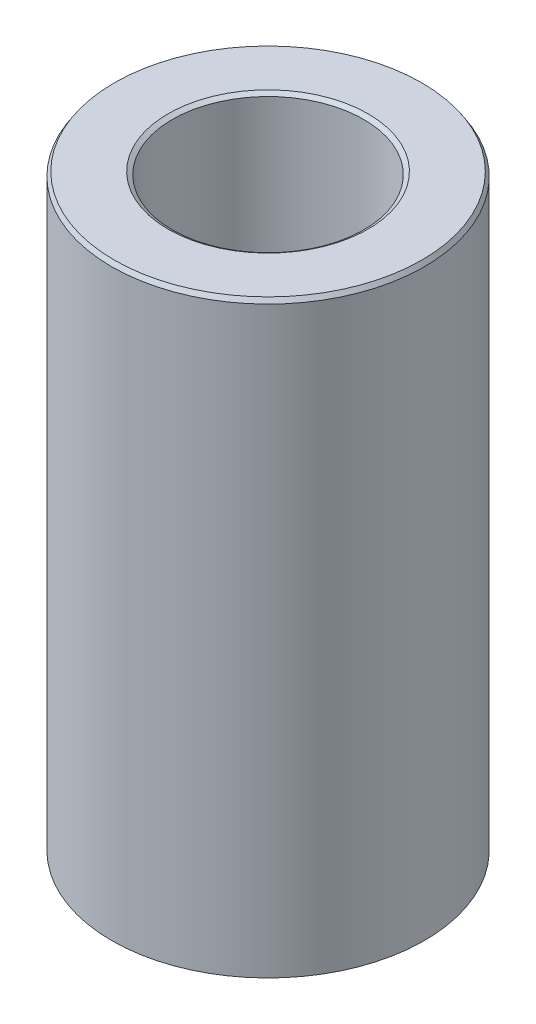
SolidWorks part; units mm, degrees
ref_plane "Front Plane" through (0, 0, 0) normal (0, 0, 1) x (1, 0, 0)
ref_plane "Top Plane" through (0, 0, 0) normal (0, 1, 0) x (1, 0, 0)
ref_plane "Right Plane" through (0, 0, 0) normal (1, 0, 0) x (0, 0, -1)
sketch "Sketch1" plane through (0, 0, 0) normal (0, 1, 0) x (1, 0, 0)
  circle A0 centre (0, 0) radius 37.5
  dimension "SLEEVE_OD" = 75
extrude "Boss-Extrude1" add sketch "Sketch1" along normal blind 141.6279
sketch "Sketch2" plane through (0, 0, 0) normal (0, 1, 0) x (1, 0, 0)
  circle A0 centre (0, 0) radius 22.9434
  dimension "BORE_D" = 45.8868
extrude "Cut-Extrude1" cut sketch "Sketch2" along normal through all
chamfer "Chamfer1" distance 1.0323 angle 32.569 4 edges at (0, 141.6279, 22.9434) (0, 0, 22.9434) (0, 0, 37.5) (0, 141.6279, 37.5) first distance on face at (0, 141.6279, 22.9434) first distance on face at (0, 0, 22.9434) first distance on face at (0, 141.6279, 37.5)
